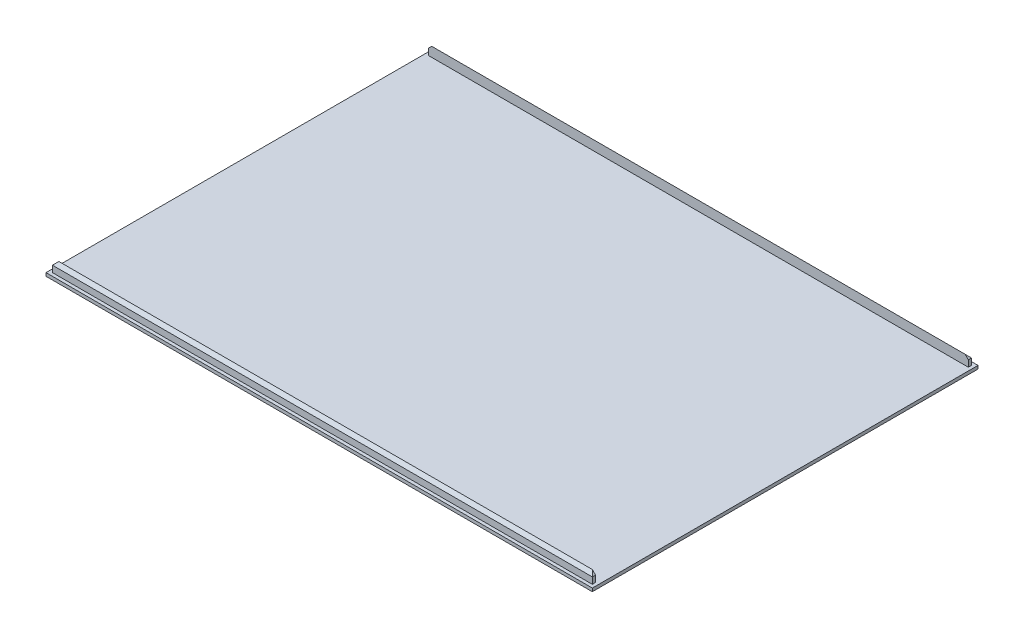
SolidWorks part; units mm, degrees
ref_plane "Front Plane" through (0, 0, 0) normal (0, 0, 1) x (1, 0, 0)
ref_plane "Top Plane" through (0, 0, 0) normal (0, 1, 0) x (1, 0, 0)
ref_plane "Right Plane" through (0, 0, 0) normal (1, 0, 0) x (0, 0, -1)
sketch "Sketch1" plane through (0, 0, 0) normal (0, 1, 0) x (1, 0, 0)
  line L1 (0, 0) -> (170, 0)
  line L2 (0, 0) -> (0, 120)
  line L3 (0, 120) -> (170, 120)
  line L4 (170, 0) -> (170, 120)
  dimension "D1" = 120
  dimension "D2" = 170
extrude "Boss-Extrude1" add sketch "Sketch1" along normal blind 1
sketch "Sketch2" plane through (0, 1, 0) normal (0, 1, 0) x (1, 0, 0)
  line L0 (0, 0) -> (170, 0) construction
  line L1 (1, 1) -> (169, 1)
  line L2 (1, 1) -> (1, 2)
  line L3 (1, 2) -> (169, 2)
  line L4 (169, 1) -> (169, 2)
  line L5 (0, 120) -> (0, 0) construction
  dimension "D1" = 168
  dimension "D2" = 1
  dimension "D3" = 1
  dimension "D4" = 1
extrude "Boss-Extrude2" add sketch "Sketch2" along normal blind 3
chamfer "Chamfer1" distance 1 angle 45 3 edges at (85, 4, -1) (169, 4, -1.5) (1, 4, -1.5)
ref_plane "Plane1" through (0, 0, -60) normal (0, 0, 1) x (1, 0, 0)
mirror "Mirror1" about plane through (0, 0, -60) normal (0, 0, 1) of "Boss-Extrude2", "Chamfer1"
sketch "Sketch3" plane through (0, 0, 0) normal (0, -1, 0) x (1, 0, 0)
  line L0 (0, -120) -> (0, 0) construction
  line L1 (0, 0) -> (170, 0) construction
  text T0 "ARDUINO &\r\nSOLENOID" font "Century Gothic" height 16
  dimension "D1" = 15
  dimension "D2" = 40
extrude "Cut-Extrude1" cut sketch "Sketch3" against normal blind 0.2
